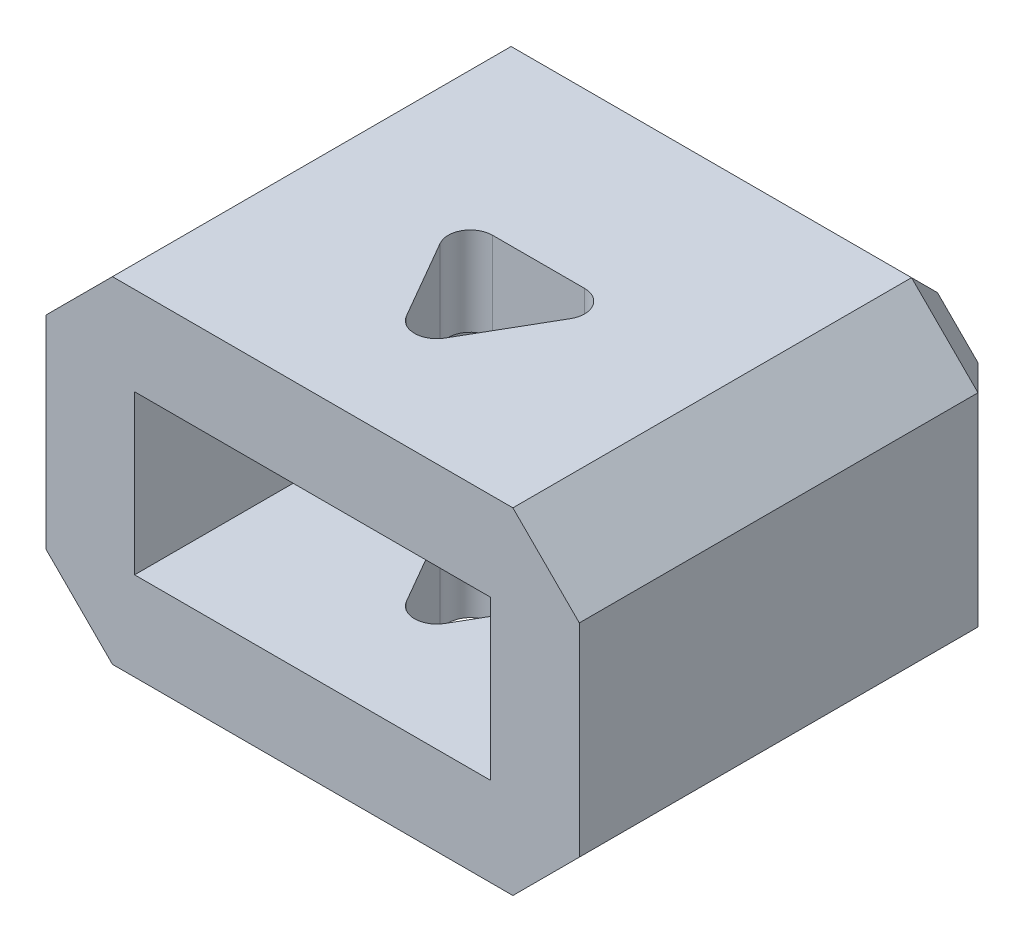
SolidWorks part; units mm, degrees
ref_plane "Front Plane" through (0, 0, 0) normal (0, 0, 1) x (1, 0, 0)
ref_plane "Top Plane" through (0, 0, 0) normal (0, 1, 0) x (1, 0, 0)
ref_plane "Right Plane" through (0, 0, 0) normal (1, 0, 0) x (0, 0, -1)
sketch "Sketch1" plane through (0, 0, 0) normal (0, 0, 1) x (1, 0, 0)
  line L1 (4.02, -1.79) -> (-4.02, -1.79)
  line L2 (4.02, -1.79) -> (4.02, 1.79)
  line L3 (4.02, 1.79) -> (-4.02, 1.79)
  line L4 (-4.02, -1.79) -> (-4.02, 1.79)
  line L5 (0, 1.79) -> (0, -1.79) construction
  line L6 (4.02, 0) -> (-4.02, 0) construction
  line L7 (-6.02, 3.79) -> (6.02, 3.79)
  line L8 (-6.02, 3.79) -> (-6.02, -3.79)
  line L9 (-6.02, -3.79) -> (6.02, -3.79)
  line L10 (6.02, 3.79) -> (6.02, -3.79)
  line L11 (0, -3.79) -> (0, 3.79) construction
  line L12 (-6.02, 0) -> (6.02, 0) construction
  point P0 (0, 0)
  point P4 (0, 0)
  dimension "D1" = 3.58
  dimension "D2" = 8.04
  dimension "D3" = 2
  dimension "D4" = 2
extrude "Boss-Extrude1" add sketch "Sketch1" along normal blind 8
extrude "Boss-Extrude2" add sketch "Sketch1<2>" against normal blind 2 contours L4 L1 L2 L3 | L10 L7 L8 L9 L1 L4 L3 L2 region at (0, 0, 0) region at (0, 3.6477, 0)
sketch "Sketch1<2>" plane through (0, 0, 0) normal (0, 0, 1) x (1, 0, 0) same geometry as "Sketch1"
chamfer "Chamfer1" distance 1.5 angle 45 4 edges at (-6.02, -3.79, 3) (-6.02, 3.79, 3) (6.02, 3.79, 3) (6.02, -3.79, 3)
sketch "Sketch2" plane through (0, -3.79, 0) normal (0, -1, 0) x (1, 0, 0)
  line L0 (-4.52, -2) -> (4.52, -2) construction
  line L1 (-1.9053, 2.9) -> (1.9053, 2.9)
  line L2 (1.9053, 2.9) -> (0, 6.2)
  line L3 (0, 6.2) -> (-1.9053, 2.9)
  circle A0 centre (0, 4) radius 1.1 construction
  dimension "D2" = 2.2
  dimension "D1" = 4
extrude "Cut-Extrude1" cut sketch "Sketch2" against normal through all both and the other way through all
fillet "Fillet1" radius 0.5 6 edges at (-1.9053, 2.79, 2.9) (0, 2.79, 6.2) (1.9053, 2.79, 2.9) (1.9053, -2.79, 2.9) (0, -2.79, 6.2) (-1.9053, -2.79, 2.9)
chamfer "Chamfer2" distance 1 angle 45 8 edges at (5.27, -3.04, -2) (6.02, 0, -2) (5.27, 3.04, -2) (0, 3.79, -2) (-5.27, 3.04, -2) (-6.02, 0, -2) (-5.27, -3.04, -2) (0, -3.79, -2)
equation "\"LF\" = 0.04mm"
equation "\"TF\" = 0.02mm"
equation "\"AngLF\"= 0.5deg"
equation "\"AngTF\"= 0.3deg"
equation "\"D2@Sketch1\"=8+2*\"TF\""
equation "\"D1@Sketch1\"=3.5+2*\"LF\""
